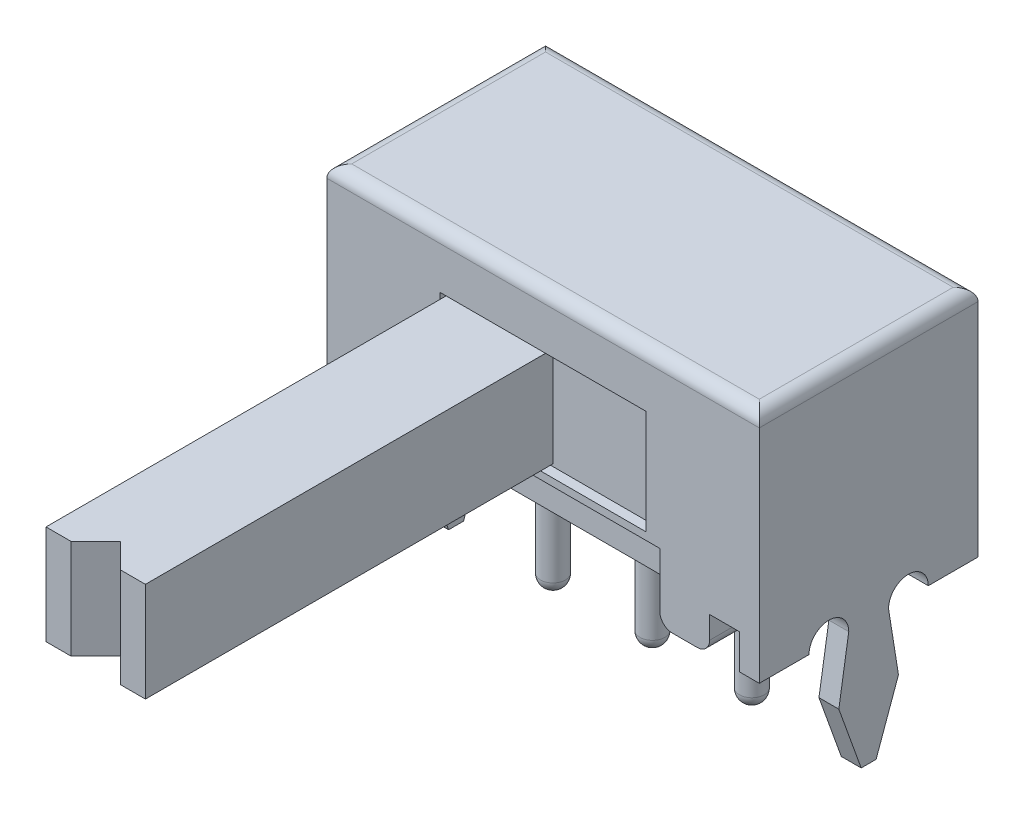
SolidWorks part; units mm, degrees
ref_plane "Front Plane" through (0, 0, 0) normal (0, 0, 1) x (1, 0, 0)
ref_plane "Top Plane" through (0, 0, 0) normal (0, 1, 0) x (1, 0, 0)
ref_plane "Right Plane" through (0, 0, 0) normal (1, 0, 0) x (0, 0, -1)
sketch "Top Profile" plane through (0, 0, 0) normal (0, 1, 0) x (1, 0, 0)
  line L1 (4.35, -2.2) -> (-4.35, -2.2)
  line L2 (4.35, -2.2) -> (4.35, 2.2)
  line L3 (4.35, 2.2) -> (-4.35, 2.2)
  line L4 (-4.35, -2.2) -> (-4.35, 2.2)
  line L5 (0, 2.2) -> (0, -2.2) construction
  line L6 (4.35, 0) -> (-4.35, 0) construction
  point P0 (0, 0)
  dimension "D1" = 8.7
  dimension "D2" = 4.4
sketch "Pins" plane through (0, 0, 0) normal (0, 1, 0) x (1, 0, 0)
  line L0 (4.35, -2.2) -> (-4.35, -2.2) construction
  line L1 (4.35, -2.2) -> (4.35, 2.2) construction
  line L2 (4.35, 2.2) -> (-4.35, 2.2) construction
  line L3 (-4.35, -2.2) -> (-4.35, 2.2) construction
  line L4 (4.35, -2.2) -> (-4.35, -2.2) construction
  line L5 (4.35, -2.2) -> (4.35, 2.2) construction
  line L6 (4.35, 2.2) -> (-4.35, 2.2) construction
  line L7 (-4.35, -2.2) -> (-4.35, 2.2) construction
  line L8 (2, 0) -> (-2, 0) construction
  line L14 (-3.95, -0.6) -> (-4.35, -0.6)
  line L15 (4.15, 0) -> (-4.15, 0) construction
  line L16 (-3.95, -0.6) -> (-3.95, 0.6)
  line L17 (-3.95, 0.6) -> (-4.35, 0.6)
  line L18 (-4.35, -0.6) -> (-4.35, 0.6)
  line L19 (-4.15, 0.6) -> (-4.15, -0.6) construction
  line L20 (-3.95, 0) -> (-4.35, 0) construction
  line L21 (4.35, -0.6) -> (3.95, -0.6)
  line L22 (4.35, -0.6) -> (4.35, 0.6)
  line L23 (4.35, 0.6) -> (3.95, 0.6)
  line L24 (3.95, -0.6) -> (3.95, 0.6)
  line L25 (4.15, 0.6) -> (4.15, -0.6) construction
  line L26 (4.35, 0) -> (3.95, 0) construction
  circle A0 centre (0, 0) radius 0.25
  circle A1 centre (-2, 0) radius 0.25
  circle A2 centre (2, 0) radius 0.25
  dimension "D1" = 0.5
  dimension "D2" = 1.2
  dimension "D3" = 4
  dimension "D4" = 8.3
  dimension "D5" = 0.4
sketch "Side Profile" plane through (0, 0, 0) normal (1, 0, 0) x (0, 0, -1)
  line L0 (-2.2, 0) -> (-2.2, 4.7) construction
  line L1 (-2.2, 4.7) -> (2.2, 4.7)
  line L2 (2.2, 4.7) -> (2.2, 0) construction
  line L3 (-2.2, 0.7) -> (-2.2, 0)
  line L4 (2.2, 4.7) -> (-2.2, 4.7) construction
  line L5 (2.2, 4.7) -> (2.2, 0.7)
  line L6 (2.2, 0.7) -> (-2.2, 0.7) construction
  line L7 (-2.2, 4.7) -> (-2.2, 0.7)
  line L8 (2.2, 4.7) -> (-2.2, 0.7) construction
  line L9 (2.2, 0.7) -> (-2.2, 4.7) construction
  line L10 (2.2, 0.7) -> (2.2, 0)
  line L11 (2.2, 0) -> (-2.2, 0) construction
  line L12 (-1.2, 0) -> (-2.2, 0)
  line L13 (1.2, 0) -> (2.2, 0)
  line L14 (-0.4, 0) -> (-0.6, -1.25)
  line L15 (-0.6, -1.25) -> (-0.15, -2.5)
  line L16 (-0.15, -2.5) -> (0.15, -2.5)
  line L17 (0.15, -2.5) -> (0.6, -1.25)
  line L18 (0.6, -1.25) -> (0.4, 0)
  line L19 (0, 0) -> (0, -2.5) construction
  line L20 (-0.6, -1.25) -> (0.6, -1.25) construction
  line L21 (-2.2, 0) -> (2.2, 0) construction
  line L22 (-0.4, 0) -> (0.4, 0)
  line L23 (-0.4, 0) -> (-1.2, 0)
  line L24 (1.2, 0) -> (0.4, 0)
  line L25 (-0.8, 0.4) -> (0.8, 0.4)
  arc A0 (-1.2, 0) -> (-0.4, 0) centre (-0.8, 0) cw
  arc A1 (0.4, 0) -> (1.2, 0) centre (0.8, 0) cw
  point P8 (0, 2.7)
  point P23 (0, -1.25)
  dimension "D7" = 0.4
  dimension "D1" = 4.7
  dimension "D2" = 4
  dimension "D3" = 2.5
  dimension "D4" = 1.2
  dimension "D5" = 0.3
  dimension "D6" = 1
extrude "Base" add sketch "Top Profile" along normal up to vertex (4.7 mm away) from vertex contours L4 L1 L2 L3 region at (0, 0, 0) up to point (0, 4.7, 2.2) starting at point (0, 0.7, 2.2)
sketch "Front Profile" plane through (0, 0, 0) normal (0, 0, 1) x (1, 0, 0)
  line L0 (0, 0.7) -> (0, 0) construction
  line L1 (4.35, 0.7) -> (-4.35, 0.7) construction
  line L2 (4.35, 0.7) -> (4.35, 4.7)
  line L3 (4.35, 4.7) -> (-4.35, 4.7)
  line L4 (-4.35, 0.7) -> (-4.35, 4.7)
  line L5 (0, 4.7) -> (0, 0.7) construction
  line L6 (4.35, 2.7) -> (-4.35, 2.7) construction
  line L7 (2.075, 1.5) -> (-2.075, 1.5)
  line L8 (2.075, 1.5) -> (2.075, 3.6)
  line L9 (2.075, 3.6) -> (-2.075, 3.6)
  line L10 (-2.075, 1.5) -> (-2.075, 3.6)
  line L11 (0, 3.6) -> (0, 1.5) construction
  line L12 (2.075, 2.55) -> (-2.075, 2.55) construction
  line L13 (-2, 3.55) -> (0, 3.55)
  line L14 (-2, 3.55) -> (-2, 1.55)
  line L15 (-2, 1.55) -> (0, 1.55)
  line L16 (0, 3.55) -> (0, 1.55)
  line L17 (-2, 3.55) -> (0, 1.55) construction
  line L18 (-2, 1.55) -> (0, 3.55) construction
  line L19 (-2.075, 1.5) -> (-2.075, 1.35) construction
  line L20 (-2.35, 0.7) -> (-2.35, 0.25)
  line L21 (-2.6, 0) -> (-3.1, 0)
  line L22 (-3.35, 0.25) -> (-3.35, 0.7)
  line L23 (-3.35, 0.7) -> (-4.35, 0.7)
  line L24 (2.075, 1.5) -> (2.075, 1.35) construction
  line L25 (2.35, 0.7) -> (2.35, 0.25)
  line L26 (2.6, 0) -> (3.1, 0)
  line L27 (3.35, 0.25) -> (3.35, 0.7)
  line L28 (3.35, 0.7) -> (4.35, 0.7)
  line L29 (2.35, 0) -> (-2.35, 0) construction
  line L30 (-2.35, 0.7) -> (-2.35, 1.35)
  line L31 (-2.35, 1.35) -> (2.35, 1.35)
  line L32 (2.35, 1.35) -> (2.35, 0.7)
  line L33 (-2.35, 0) -> (-2.6, 0) construction
  line L34 (2.35, 0) -> (2.6, 0) construction
  line L35 (2.35, 0.25) -> (2.35, 0) construction
  line L36 (-2.35, 0.25) -> (-2.35, 0) construction
  line L37 (-2.35, 0.7) -> (2.35, 0.7)
  arc A0 (-3.1, 0) -> (-3.35, 0.25) centre (-3.1, 0.25) cw
  arc A1 (3.1, 0) -> (3.35, 0.25) centre (3.1, 0.25) ccw
  arc A2 (2.35, 0.25) -> (2.6, 0) centre (2.6, 0.25) ccw
  arc A3 (-2.35, 0.25) -> (-2.6, 0) centre (-2.6, 0.25) cw
  point P0 (0, 2.7)
  point P4 (0, 2.7)
  point P12 (-1, 2.55)
  point P25 (0, 0)
  point P27 (-3.35, 0)
  dimension "D9" = 0.25
  dimension "D10" = 0.25
  dimension "D1" = 4.15
  dimension "D2" = 2.55
  dimension "D3" = 2.1
  dimension "D4" = 2
  dimension "D5" = 2
  dimension "D6" = 1
  dimension "D7" = 1
  dimension "D8" = 0.15
  dimension "D11" = 1
extrude "Base Extrude" add sketch "Front Profile" along normal up to vertex (2.2 mm away) from vertex contours L4 L3 L2 L28 L27 A1 L26 A2 L25 L32 L31 L30 L20 A3 L21 A0 L22 L23 up to point (-4.35, 0, 2.2) starting at point (-4.35, 0, -2.2)
extrude "Bottom Front Cutout" cut sketch "Front Profile<4>" against normal blind 0.2 from surface contours L30 L37 L32 L31 region at (0, 1.025, 0) starting at face at (0, 0.8996, 2.2)
sketch "Front Profile<4>" plane through (0, 0, 0) normal (0, 0, 1) x (1, 0, 0) same geometry as "Front Profile"
extrude "Bottom Rear Cutout" cut sketch "Front Profile<5>" along normal blind 0.2 from surface contours L30 L37 L32 L31 region at (0, 1.025, 0) starting at face at (0, 0.8996, -2.2)
sketch "Front Profile<5>" plane through (0, 0, 0) normal (0, 0, 1) x (1, 0, 0) same geometry as "Front Profile"
extrude "Switch Inset" cut sketch "Front Profile<6>" against normal blind 0.2 from surface contours L16 L13 L14 L15 | L10 L7 L8 L9 L13 L16 L15 L14 region at (0.8484, 2.55, 0) region at (-1, 2.55, 0) starting at face at (0, 0.9808, 2.2)
sketch "Front Profile<6>" plane through (0, 0, 0) normal (0, 0, 1) x (1, 0, 0) same geometry as "Front Profile"
extrude "Undercut Notch" cut sketch "Side Profile" against normal through all both and the other way through all contours A0 L23 | A1 L24 | L22 A1 L25 A0 region at (0, 0.1698, 0.8) region at (0, 0.1698, -0.8) region at (0, 0.2196, 0)
extrude "Lever" add sketch "Front Profile<7>" along normal blind 8 and the other way up to surface from surface contours L16 L13 L14 L15 region at (-1, 2.55, 0) other way up to plane "Front Plane" starting at face at (0, 0.9808, 2.2)
sketch "Front Profile<7>" plane through (0, 0, 0) normal (0, 0, 1) x (1, 0, 0) same geometry as "Front Profile"
extrude "Right Pin" add sketch "Side Profile<5>" against normal blind 0.4 from surface contours L22 L14 L15 L16 L17 L18 | L22 A1 L25 A0 | L25 A1 L13 L10 L5 L1 L7 L3 L12 A0 region at (0, 2.4472, 0) region at (0, -1.131, 0) region at (0, 0.2196, 0) starting at face at (4.35, 2.7, 0)
sketch "Side Profile<5>" plane through (0, 0, 0) normal (1, 0, 0) x (0, 0, -1) same geometry as "Side Profile"
extrude "Left Pin" add sketch "Side Profile<6>" along normal blind 0.4 from surface contours L22 L14 L15 L16 L17 L18 | L22 A1 L25 A0 | L25 A1 L13 L10 L5 L1 L7 L3 L12 A0 region at (0, 2.4472, 0) region at (0, -1.131, 0) region at (0, 0.2196, 0) starting at face at (-4.35, 2.7, 0)
sketch "Side Profile<6>" plane through (0, 0, 0) normal (1, 0, 0) x (0, 0, -1) same geometry as "Side Profile"
extrude "Electrical Pins" add sketch "Pins" against normal blind 2.6 and the other way up to surface (0.7 mm away) contours A1 | A0 | A2 region at (0, 0, 0) region at (-2, 0, 0) region at (2, 0, 0) other way up to face at (0, 0.7, 0)
ref_plane "Lever Tip Plane" through (0, 0, 10.2) normal (0, 0, 1) x (1, 0, 0)
ref_axis "Lever Edge Center" through (-1, 3.55, 10.2) along (0, -1, 0)
sketch "Lever Notch Profile" plane through (0, 0, 0) normal (0, 1, 0) x (1, 0, 0)
  line L0 (-1.5, -10.2) -> (-0.5, -10.2)
  line L1 (-0.5, -10.2) -> (-1, -9.7)
  line L2 (-1, -9.7) -> (-1.5, -10.2)
  line L3 (-1.1, -10.2) -> (1.1, -10.2) construction
  line L4 (-1.5, -10.2) -> (-1.7869, -10.2) construction
  line L5 (-0.5, -10.2) -> (0, -10.2) construction
  line L6 (-1, -9.7) -> (-1, -10.2) construction
  point P5 (-1, -10.2)
  dimension "D1" = 1
  dimension "D2" = 45
extrude "Lever Notch" cut sketch "Lever Notch Profile" along normal through all both and the other way through all
fillet "Top Fillet" radius 0.25 4 edges at (0, 4.7, 2.2) (4.35, 4.7, 0) (0, 4.7, -2.2) (-4.35, 4.7, 0)
fillet "Pin Fillet" radius 0.25 3 edges at (2, -2.6, 0.25) (0, -2.6, 0.25) (-2, -2.6, 0.25)
equation "\"Lever-Length\" = 8mm"
equation "\"D1@Lever\"=\"Lever-Length\""
